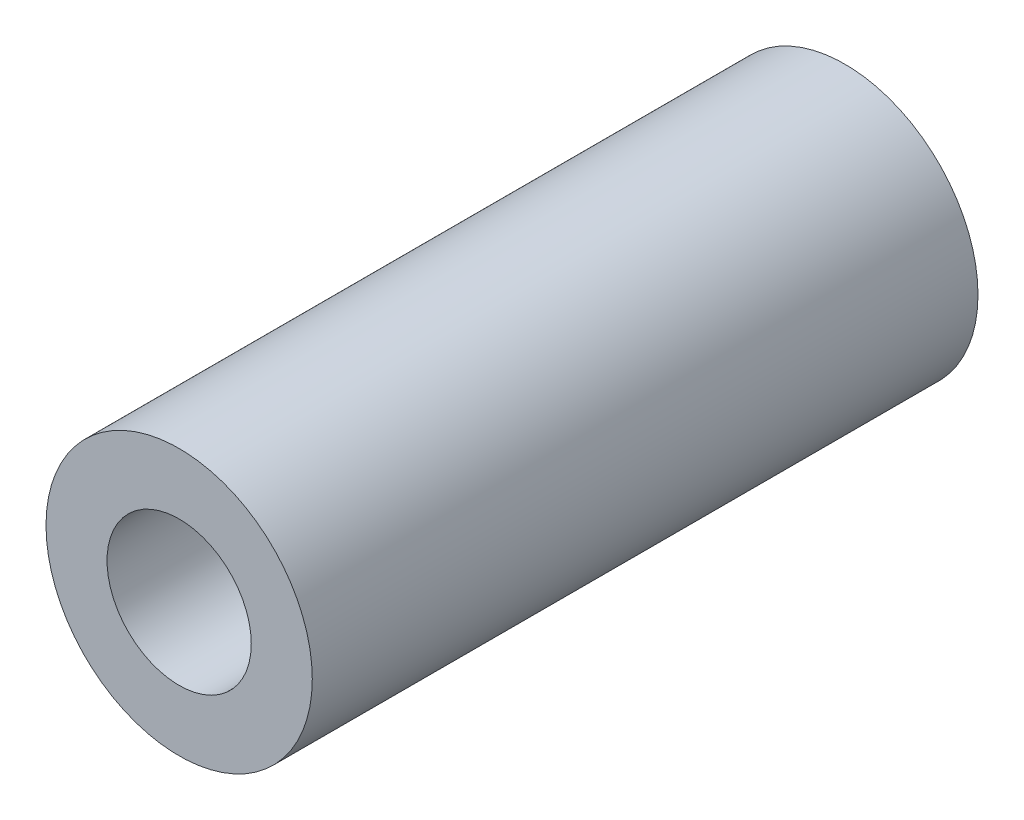
SolidWorks part; units mm, degrees
material "ABS"
ref_plane "Front Plane" through (0, 0, 0) normal (0, 0, 1) x (1, 0, 0)
ref_plane "Top Plane" through (0, 0, 0) normal (0, 1, 0) x (1, 0, 0)
ref_plane "Right Plane" through (0, 0, 0) normal (1, 0, 0) x (0, 0, -1)
sketch "Sketch1" plane through (0, 0, 0) normal (0, 0, 1) x (1, 0, 0)
  circle A0 centre (0, 0) radius 6
  circle A1 centre (0, 0) radius 3.25
  circle A2 centre (0, 0) radius 4
  dimension "D1" = 12
  dimension "D2" = 6.5
  dimension "D3" = 8
extrude "Boss-Extrude1" add sketch "Sketch1" along normal blind 25 and the other way blind 5 contours A2 A1 | A0 A2 | A1 region at (-5.8303, 0, 0) region at (0, 0, 0) region at (-3.8869, 0, 0)
extrude "Cut-Extrude1" cut sketch "Sketch1<4>" against normal blind 25 from offset 25 contours A1
sketch "Sketch1<4>" plane through (0, 0, 0) normal (0, 0, 1) x (1, 0, 0) same geometry as "Sketch1"
